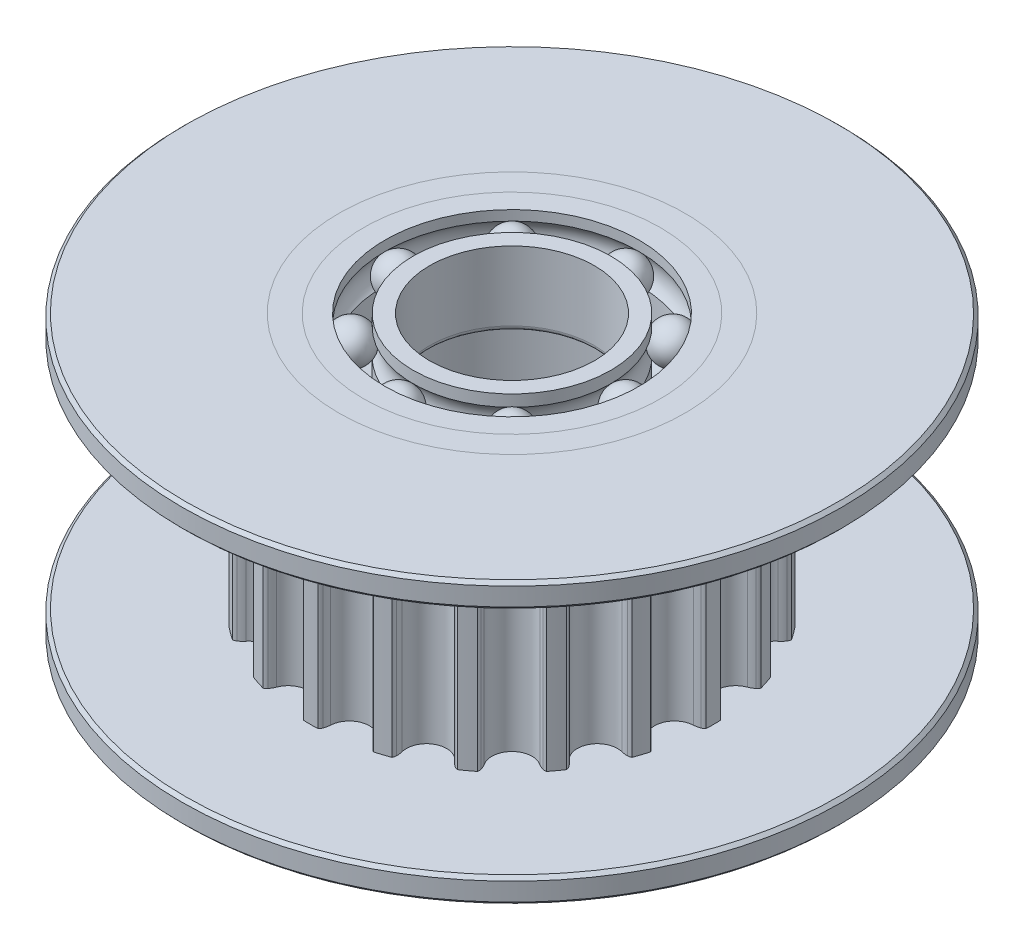
SolidWorks part; units mm, degrees
material "6061-T6 (SS)"
ref_plane "Přední rovina" through (0, 0, 0) normal (0, 0, 1) x (1, 0, 0)
ref_plane "Horní rovina" through (0, 0, 0) normal (0, 1, 0) x (1, 0, 0)
ref_plane "Pravá rovina" through (0, 0, 0) normal (1, 0, 0) x (0, 0, -1)
sketch "Skica1" plane through (0, 0, 0) normal (0, 0, 1) x (1, 0, 0)
  line L0 (4.5, 10) -> (5.25, 10)
  line L1 (5.25, 10) -> (5.25, 8.5)
  line L2 (5.25, 8.5) -> (6.11, 8.5)
  line L3 (6.11, 8.5) -> (6.11, 1.5)
  line L4 (6.11, 1.5) -> (5.25, 1.5)
  line L5 (5.25, 1.5) -> (5.25, 0)
  line L6 (5.25, 0) -> (4.5, 0)
  line L8 (4.5, 10) -> (4.5, 7)
  line L9 (4.5, 7) -> (3.5, 7)
  line L10 (3.5, 7) -> (3.5, 3)
  line L11 (3.5, 3) -> (4.5, 3)
  line L12 (4.5, 3) -> (4.5, 0)
  line L13 (0, 0) -> (0, -4.1646) construction
  dimension "D1" = 10
  dimension "D2" = 7
  dimension "D3" = 4.5
  dimension "D4" = 3.5
  dimension "D5" = 6.11
  dimension "D6" = 3
  dimension "D7" = 5.25
revolve "Rotovat1" add sketch "Skica1" angle 360 about L13
chamfer "Zkosení1" distance 0.1 angle 45 4 edges at (0, 3, 3.5) (0, 0, 4.5) (0, 7, 3.5) (0, 10, 4.5)
fillet "Zaoblit1" radius 0.1 2 edges at (0, 3, 4.5) (0, 7, 4.5)
sketch "Skica11" plane through (0, 8.5, 0) normal (0, 1, 0) x (1, 0, 0)
  line L0 (0, -5.5) -> (0, 5.5) construction
  line L1 (-5.5, 0) -> (5.5, 0) construction
  point P5 (0, 6.1087)
  arc B0 (-3.6824, -4.5256) -> (-4.5256, -3.6824) centre (-4.1938, -4.1938) ccw
  arc B1 (-3.6824, -4.5256) -> (-3.7624, -4.7003) centre (-3.1284, -4.885) ccw
  arc B2 (-3.7624, -4.7003) -> (-3.7672, -4.8088) centre (-3.5429, -4.7643) ccw
  arc B3 (-3.7672, -4.8088) -> (-3.4093, -5.0688) centre (0, 0) ccw
  arc B4 (-3.4093, -5.0688) -> (-3.3076, -5.0308) centre (-3.4362, -4.8418) ccw
  arc B5 (-3.3076, -5.0308) -> (-3.1662, -4.9006) centre (-3.6792, -4.4848) ccw
  arc B6 (-2.1037, -5.442) -> (-3.1662, -4.9006) centre (-2.6926, -5.2845) ccw
  arc B7 (-2.1037, -5.442) -> (-2.1258, -5.6329) centre (-1.4657, -5.6126) ccw
  arc B8 (-2.1258, -5.6329) -> (-2.0968, -5.7376) centre (-1.8973, -5.6259) ccw
  arc B9 (-2.0968, -5.7376) -> (-1.6761, -5.8742) centre (0, 0) ccw
  arc B10 (-1.6761, -5.8742) -> (-1.5911, -5.8066) centre (-1.7719, -5.6667) ccw
  arc B11 (-1.5911, -5.8066) -> (-1.4968, -5.6392) centre (-2.1132, -5.4022) ccw
  arc B12 (-0.319, -5.8257) -> (-1.4968, -5.6392) centre (-0.9278, -5.8579) ccw
  arc B13 (-0.319, -5.8257) -> (-0.2811, -6.0141) centre (0.3404, -5.7909) ccw
  arc B14 (-0.2811, -6.0141) -> (-0.2211, -6.1047) centre (-0.0659, -5.9369) ccw
  arc B15 (-0.2211, -6.1047) -> (0.2211, -6.1047) centre (0, 0) ccw
  arc B16 (0.2211, -6.1047) -> (0.2811, -6.0141) centre (0.0659, -5.9369) ccw
  arc B17 (0.2811, -6.0141) -> (0.319, -5.8257) centre (-0.3404, -5.7909) ccw
  arc B18 (1.4968, -5.6392) -> (0.319, -5.8257) centre (0.9278, -5.8579) ccw
  arc B19 (1.4968, -5.6392) -> (1.5911, -5.8066) centre (2.1132, -5.4022) ccw
  arc B20 (1.5911, -5.8066) -> (1.6761, -5.8742) centre (1.7719, -5.6667) ccw
  arc B21 (1.6761, -5.8742) -> (2.0968, -5.7376) centre (0, 0) ccw
  arc B22 (2.0968, -5.7376) -> (2.1258, -5.6329) centre (1.8973, -5.6259) ccw
  arc B23 (2.1258, -5.6329) -> (2.1037, -5.442) centre (1.4657, -5.6126) ccw
  arc B24 (3.1662, -4.9006) -> (2.1037, -5.442) centre (2.6926, -5.2845) ccw
  arc B25 (3.1662, -4.9006) -> (3.3076, -5.0308) centre (3.6792, -4.4848) ccw
  arc B26 (3.3076, -5.0308) -> (3.4093, -5.0688) centre (3.4362, -4.8418) ccw
  arc B27 (3.4093, -5.0688) -> (3.7672, -4.8088) centre (0, 0) ccw
  arc B28 (3.7672, -4.8088) -> (3.7624, -4.7003) centre (3.5429, -4.7643) ccw
  arc B29 (3.7624, -4.7003) -> (3.6824, -4.5256) centre (3.1284, -4.885) ccw
  arc B30 (4.5256, -3.6824) -> (3.6824, -4.5256) centre (4.1938, -4.1938) ccw
  arc B31 (4.5256, -3.6824) -> (4.7003, -3.7624) centre (4.885, -3.1284) ccw
  arc B32 (4.7003, -3.7624) -> (4.8088, -3.7672) centre (4.7643, -3.5429) ccw
  arc B33 (4.8088, -3.7672) -> (5.0688, -3.4093) centre (0, 0) ccw
  arc B34 (5.0688, -3.4093) -> (5.0308, -3.3076) centre (4.8418, -3.4362) ccw
  arc B35 (5.0308, -3.3076) -> (4.9006, -3.1662) centre (4.4848, -3.6792) ccw
  arc B36 (5.442, -2.1037) -> (4.9006, -3.1662) centre (5.2845, -2.6926) ccw
  arc B37 (5.442, -2.1037) -> (5.6329, -2.1258) centre (5.6126, -1.4657) ccw
  arc B38 (5.6329, -2.1258) -> (5.7376, -2.0968) centre (5.6259, -1.8973) ccw
  arc B39 (5.7376, -2.0968) -> (5.8742, -1.6761) centre (0, 0) ccw
  arc B40 (5.8742, -1.6761) -> (5.8066, -1.5911) centre (5.6667, -1.7719) ccw
  arc B41 (5.8066, -1.5911) -> (5.6392, -1.4968) centre (5.4022, -2.1132) ccw
  arc B42 (5.8257, -0.319) -> (5.6392, -1.4968) centre (5.8579, -0.9278) ccw
  arc B43 (5.8257, -0.319) -> (6.0141, -0.2811) centre (5.7909, 0.3404) ccw
  arc B44 (6.0141, -0.2811) -> (6.1047, -0.2211) centre (5.9369, -0.0659) ccw
  arc B45 (6.1047, -0.2211) -> (6.1047, 0.2211) centre (0, 0) ccw
  arc B46 (6.1047, 0.2211) -> (6.0141, 0.2811) centre (5.9369, 0.0659) ccw
  arc B47 (6.0141, 0.2811) -> (5.8257, 0.319) centre (5.7909, -0.3404) ccw
  arc B48 (5.6392, 1.4968) -> (5.8257, 0.319) centre (5.8579, 0.9278) ccw
  arc B49 (5.6392, 1.4968) -> (5.8066, 1.5911) centre (5.4022, 2.1132) ccw
  arc B50 (5.8066, 1.5911) -> (5.8742, 1.6761) centre (5.6667, 1.7719) ccw
  arc B51 (5.8742, 1.6761) -> (5.7376, 2.0968) centre (0, 0) ccw
  arc B52 (5.7376, 2.0968) -> (5.6329, 2.1258) centre (5.6259, 1.8973) ccw
  arc B53 (5.6329, 2.1258) -> (5.442, 2.1037) centre (5.6126, 1.4657) ccw
  arc B54 (4.9006, 3.1662) -> (5.442, 2.1037) centre (5.2845, 2.6926) ccw
  arc B55 (4.9006, 3.1662) -> (5.0308, 3.3076) centre (4.4848, 3.6792) ccw
  arc B56 (5.0308, 3.3076) -> (5.0688, 3.4093) centre (4.8418, 3.4362) ccw
  arc B57 (5.0688, 3.4093) -> (4.8088, 3.7672) centre (0, 0) ccw
  arc B58 (4.8088, 3.7672) -> (4.7003, 3.7624) centre (4.7643, 3.5429) ccw
  arc B59 (4.7003, 3.7624) -> (4.5256, 3.6824) centre (4.885, 3.1284) ccw
  arc B60 (3.6824, 4.5256) -> (4.5256, 3.6824) centre (4.1938, 4.1938) ccw
  arc B61 (3.6824, 4.5256) -> (3.7624, 4.7003) centre (3.1284, 4.885) ccw
  arc B62 (3.7624, 4.7003) -> (3.7672, 4.8088) centre (3.5429, 4.7643) ccw
  arc B63 (3.7672, 4.8088) -> (3.4093, 5.0688) centre (0, 0) ccw
  arc B64 (3.4093, 5.0688) -> (3.3076, 5.0308) centre (3.4362, 4.8418) ccw
  arc B65 (3.3076, 5.0308) -> (3.1662, 4.9006) centre (3.6792, 4.4848) ccw
  arc B66 (2.1037, 5.442) -> (3.1662, 4.9006) centre (2.6926, 5.2845) ccw
  arc B67 (2.1037, 5.442) -> (2.1258, 5.6329) centre (1.4657, 5.6126) ccw
  arc B68 (2.1258, 5.6329) -> (2.0968, 5.7376) centre (1.8973, 5.6259) ccw
  arc B69 (2.0968, 5.7376) -> (1.6761, 5.8742) centre (0, 0) ccw
  arc B70 (1.6761, 5.8742) -> (1.5911, 5.8066) centre (1.7719, 5.6667) ccw
  arc B71 (1.5911, 5.8066) -> (1.4968, 5.6392) centre (2.1132, 5.4022) ccw
  arc B72 (0.319, 5.8257) -> (1.4968, 5.6392) centre (0.9278, 5.8579) ccw
  arc B73 (0.319, 5.8257) -> (0.2811, 6.0141) centre (-0.3404, 5.7909) ccw
  arc B74 (0.2811, 6.0141) -> (0.2211, 6.1047) centre (0.0659, 5.9369) ccw
  arc B75 (0.2211, 6.1047) -> (-0.2211, 6.1047) centre (0, 0) ccw
  arc B76 (-0.2211, 6.1047) -> (-0.2811, 6.0141) centre (-0.0659, 5.9369) ccw
  arc B77 (-0.2811, 6.0141) -> (-0.319, 5.8257) centre (0.3404, 5.7909) ccw
  arc B78 (-1.4968, 5.6392) -> (-0.319, 5.8257) centre (-0.9278, 5.8579) ccw
  arc B79 (-1.4968, 5.6392) -> (-1.5911, 5.8066) centre (-2.1132, 5.4022) ccw
  arc B80 (-1.5911, 5.8066) -> (-1.6761, 5.8742) centre (-1.7719, 5.6667) ccw
  arc B81 (-1.6761, 5.8742) -> (-2.0968, 5.7376) centre (0, 0) ccw
  arc B82 (-2.0968, 5.7376) -> (-2.1258, 5.6329) centre (-1.8973, 5.6259) ccw
  arc B83 (-2.1258, 5.6329) -> (-2.1037, 5.442) centre (-1.4657, 5.6126) ccw
  arc B84 (-3.1662, 4.9006) -> (-2.1037, 5.442) centre (-2.6926, 5.2845) ccw
  arc B85 (-3.1662, 4.9006) -> (-3.3076, 5.0308) centre (-3.6792, 4.4848) ccw
  arc B86 (-3.3076, 5.0308) -> (-3.4093, 5.0688) centre (-3.4362, 4.8418) ccw
  arc B87 (-3.4093, 5.0688) -> (-3.7672, 4.8088) centre (0, 0) ccw
  arc B88 (-3.7672, 4.8088) -> (-3.7624, 4.7003) centre (-3.5429, 4.7643) ccw
  arc B89 (-3.7624, 4.7003) -> (-3.6824, 4.5256) centre (-3.1284, 4.885) ccw
  arc B90 (-4.5256, 3.6824) -> (-3.6824, 4.5256) centre (-4.1938, 4.1938) ccw
  arc B91 (-4.5256, 3.6824) -> (-4.7003, 3.7624) centre (-4.885, 3.1284) ccw
  arc B92 (-4.7003, 3.7624) -> (-4.8088, 3.7672) centre (-4.7643, 3.5429) ccw
  arc B93 (-4.8088, 3.7672) -> (-5.0688, 3.4093) centre (0, 0) ccw
  arc B94 (-5.0688, 3.4093) -> (-5.0308, 3.3076) centre (-4.8418, 3.4362) ccw
  arc B95 (-5.0308, 3.3076) -> (-4.9006, 3.1662) centre (-4.4848, 3.6792) ccw
  arc B96 (-5.442, 2.1037) -> (-4.9006, 3.1662) centre (-5.2845, 2.6926) ccw
  arc B97 (-5.442, 2.1037) -> (-5.6329, 2.1258) centre (-5.6126, 1.4657) ccw
  arc B98 (-5.6329, 2.1258) -> (-5.7376, 2.0968) centre (-5.6259, 1.8973) ccw
  arc B99 (-5.7376, 2.0968) -> (-5.8742, 1.6761) centre (0, 0) ccw
  arc B100 (-5.8742, 1.6761) -> (-5.8066, 1.5911) centre (-5.6667, 1.7719) ccw
  arc B101 (-5.8066, 1.5911) -> (-5.6392, 1.4968) centre (-5.4022, 2.1132) ccw
  arc B102 (-5.8257, 0.319) -> (-5.6392, 1.4968) centre (-5.8579, 0.9278) ccw
  arc B103 (-5.8257, 0.319) -> (-6.0141, 0.2811) centre (-5.7909, -0.3404) ccw
  arc B104 (-6.0141, 0.2811) -> (-6.1047, 0.2211) centre (-5.9369, 0.0659) ccw
  arc B105 (-6.1047, 0.2211) -> (-6.1047, -0.2211) centre (0, 0) ccw
  arc B106 (-6.1047, -0.2211) -> (-6.0141, -0.2811) centre (-5.9369, -0.0659) ccw
  arc B107 (-6.0141, -0.2811) -> (-5.8257, -0.319) centre (-5.7909, 0.3404) ccw
  arc B108 (-5.6392, -1.4968) -> (-5.8257, -0.319) centre (-5.8579, -0.9278) ccw
  arc B109 (-5.6392, -1.4968) -> (-5.8066, -1.5911) centre (-5.4022, -2.1132) ccw
  arc B110 (-5.8066, -1.5911) -> (-5.8742, -1.6761) centre (-5.6667, -1.7719) ccw
  arc B111 (-5.8742, -1.6761) -> (-5.7376, -2.0968) centre (0, 0) ccw
  arc B112 (-5.7376, -2.0968) -> (-5.6329, -2.1258) centre (-5.6259, -1.8973) ccw
  arc B113 (-5.6329, -2.1258) -> (-5.442, -2.1037) centre (-5.6126, -1.4657) ccw
  arc B114 (-4.9006, -3.1662) -> (-5.442, -2.1037) centre (-5.2845, -2.6926) ccw
  arc B115 (-4.9006, -3.1662) -> (-5.0308, -3.3076) centre (-4.4848, -3.6792) ccw
  arc B116 (-5.0308, -3.3076) -> (-5.0688, -3.4093) centre (-4.8418, -3.4362) ccw
  arc B117 (-5.0688, -3.4093) -> (-4.8088, -3.7672) centre (0, 0) ccw
  arc B118 (-4.8088, -3.7672) -> (-4.7003, -3.7624) centre (-4.7643, -3.5429) ccw
  arc B119 (-4.7003, -3.7624) -> (-4.5256, -3.6824) centre (-4.885, -3.1284) ccw
sketch_block_instance "Blok1-1"
sketch_block "Blok1"
extrude "Odebrat vysunutím1" cut sketch "Skica11" against normal through all flip side to cut
sketch "Skica10" plane through (0, 10, 0) normal (0, 1, 0) x (1, 0, 0)
  circle A0 centre (0, 0) radius 10
  circle A1 centre (0, 0) radius 5.25 construction
  circle A2 centre (0, 0) radius 5.25
  dimension "D1" = 20
extrude "Přidat vysunutím1" add sketch "Skica10" against normal up to surface (1.5 mm away) separate body up to face at (0, 8.5, 5.25)
sketch "Skica12" plane through (0, 0, 0) normal (0, -1, 0) x (1, 0, 0)
  circle A0 centre (0, 0) radius 10
  circle A1 centre (0, 0) radius 5.25 construction
  circle A2 centre (0, 0) radius 5.25
  circle A3 centre (0, 0) radius 10 construction
extrude "Přidat vysunutím2" add sketch "Skica12" against normal up to surface (1.5 mm away) separate body up to face at (0, 1.5, 5.25)
chamfer "Zkosení2" distance 0.1 angle 45 2 edges at (0, 8.5, -10) (0, 10, 10)
chamfer "Zkosení3" distance 0.1 angle 45 2 edges at (0, 0, -10) (0, 1.5, 10)
sketch "Skica4" plane through (0, 0, 0) normal (0, 0, 1) x (1, 0, 0)
  line L0 (4.5, 9.85) -> (4.5, 7.15)
  line L1 (4.35, 7) -> (4.2, 7)
  line L2 (4.2, 7) -> (4.2, 7.05)
  line L3 (3.85, 7.2828) -> (4.2132, 7.229)
  line L4 (3.85, 7.2828) -> (3.85, 8.0528)
  line L5 (3.85, 8.9472) -> (3.85, 9.7172)
  line L6 (3.85, 9.7172) -> (4.2132, 9.771)
  line L7 (4.35, 10) -> (4.2, 10)
  line L8 (4.2, 10) -> (4.2, 9.95)
  line L9 (0, 0) -> (0, 18.4294) construction
  line L10 (4.4, 7) -> (-4.4, 7) construction
  arc A0 (4.35, 10) -> (4.5, 9.85) centre (4.35, 9.85) cw
  arc A1 (4.35, 7) -> (4.5, 7.15) centre (4.35, 7.15) ccw
  arc A2 (4.2, 9.95) -> (4.2132, 9.771) centre (4.2, 9.86) cw
  arc A3 (3.85, 8.9472) -> (3.85, 8.0528) centre (3.45, 8.5) cw
  arc A4 (4.2, 7.05) -> (4.2132, 7.229) centre (4.2, 7.14) ccw
  point P26 (4.5, 8.5)
  point P29 (4.275, 7)
  dimension "D3" = 0.09
  dimension "D6" = 0.15
  dimension "D7" = 0.6
  dimension "D1" = 4.5
  dimension "D2" = 3.85
  dimension "D4" = 0.05
  dimension "D5" = 0.15
  dimension "D8" = 0.77
  dimension "D9" = 3
  dimension "D10" = 1.05
revolve "Rotovat2" add sketch "Skica4" angle 360 about L9
sketch "Skica5" plane through (0, 0, 0) normal (0, 0, 1) x (1, 0, 0)
  line L0 (2.5, 9.85) -> (2.5, 7.15)
  line L1 (2.65, 10) -> (2.97, 10)
  line L2 (3, 9.97) -> (3, 9.86)
  line L3 (3, 9.86) -> (3.6, 9.86)
  line L4 (3.6, 9.86) -> (3.9, 9.84)
  line L5 (3.9, 9.84) -> (4.2, 9.86)
  line L6 (4.2, 9.86) -> (4.2, 9.81)
  line L7 (4.2, 9.81) -> (3.9, 9.77)
  line L8 (3.9, 9.77) -> (3.6, 9.77)
  line L9 (3.6, 9.77) -> (3, 9.81)
  line L10 (3, 9.81) -> (3, 8.8969)
  line L11 (2.65, 7) -> (2.97, 7)
  line L12 (0, 0) -> (0, 20.363) construction
  line L13 (3, 7.03) -> (3, 7.14)
  line L21 (3, 7.19) -> (3, 8.1031)
  line L22 (3, 7.14) -> (3.6, 7.14)
  line L23 (3.6, 7.14) -> (3.8962, 7.1917)
  line L24 (3.8962, 7.1917) -> (4.1924, 7.14)
  line L25 (4.1924, 7.14) -> (4.1924, 7.19)
  line L26 (4.1924, 7.19) -> (3.8975, 7.2581)
  line L27 (3.8975, 7.2581) -> (3.5975, 7.2581)
  line L28 (3.5975, 7.2581) -> (3, 7.19)
  line L29 (-4.2, 7) -> (4.2, 7) construction
  arc A0 (2.65, 7) -> (2.5, 7.15) centre (2.65, 7.15) cw
  arc A1 (2.65, 10) -> (2.5, 9.85) centre (2.65, 9.85) ccw
  arc A2 (3, 9.97) -> (2.97, 10) centre (2.97, 9.97) ccw
  arc A3 (3, 7.03) -> (2.97, 7) centre (2.97, 7.03) cw
  arc A4 (3, 8.8969) -> (3, 8.1031) centre (3.45, 8.5) ccw
  dimension "D3" = 0.15
  dimension "D4" = 0.11
  dimension "D5" = 0.03
  dimension "D7" = 0.6
  dimension "D1" = 2.5
  dimension "D2" = 3
  dimension "D6" = 0.6
  dimension "D8" = 0.95
  dimension "D9" = 3
  dimension "D10" = 1.2
  dimension "D11" = 0.3
  dimension "D12" = 0.05
  dimension "D13" = 0.9
  dimension "D14" = 0.6
  dimension "D15" = 0.09
  dimension "D16" = 0.05
  dimension "D17" = 0.05
revolve "Rotovat3" add sketch "Skica5" angle 360 about L12
sketch "Skica6" plane through (0, 0, 0) normal (0, 0, 1) x (1, 0, 0)
  line L0 (3.45, 9.1) -> (3.45, 7.9)
  line L4 (-4.2, 7) -> (4.2, 7) construction
  arc A0 (3.45, 9.1) -> (3.45, 7.9) centre (3.45, 8.5) cw
  dimension "D1" = 0.6
  dimension "D2" = 1.5
  dimension "D3" = 3.45
revolve "Rotovat4" add sketch "Skica6" angle 360 about L0
pattern_circular "Kruhové pole1" count 8 over 360 about axis through (0, 0, 0) along (0, 1, 0) of bodies 105
sketch "Skica7" plane through (0, 0, 0) normal (0, 0, 1) x (1, 0, 0)
  line L0 (4.5, 2.85) -> (4.5, 0.15)
  line L1 (4.35, 0) -> (4.2, 0)
  line L2 (4.2, 0) -> (4.2, 0.05)
  line L3 (3.85, 0.2828) -> (4.2132, 0.229)
  line L4 (3.85, 0.2828) -> (3.85, 1.0528)
  line L5 (3.85, 1.9472) -> (3.85, 2.7172)
  line L6 (3.85, 2.7172) -> (4.2132, 2.771)
  line L7 (4.35, 3) -> (4.2, 3)
  line L8 (4.2, 3) -> (4.2, 2.95)
  line L9 (0, 0) -> (0, 11.2374) construction
  arc A0 (4.35, 3) -> (4.5, 2.85) centre (4.35, 2.85) cw
  arc A1 (4.35, 0) -> (4.5, 0.15) centre (4.35, 0.15) ccw
  arc A2 (4.2, 2.95) -> (4.2132, 2.771) centre (4.2, 2.86) cw
  arc A3 (3.85, 1.9472) -> (3.85, 1.0528) centre (3.45, 1.5) cw
  arc A4 (4.2, 0.05) -> (4.2132, 0.229) centre (4.2, 0.14) ccw
  point P19 (4.5, 1.5)
  point P20 (4.275, 0)
  dimension "D1" = 0.09
  dimension "D4" = 0.15
  dimension "D5" = 0.6
  dimension "D2" = 0.05
  dimension "D3" = 0.15
  dimension "D6" = 0.77
  dimension "D7" = 3
  dimension "D8" = 1.05
  dimension "D9" = 4.5
  dimension "D10" = 3.85
revolve "Rotovat5" add sketch "Skica7" angle 360 about L9
sketch "Skica8" plane through (0, 0, 0) normal (0, 0, 1) x (1, 0, 0)
  line L0 (2.5, 2.85) -> (2.5, 0.15)
  line L1 (2.65, 3) -> (2.97, 3)
  line L2 (3, 2.97) -> (3, 2.86)
  line L3 (3, 2.86) -> (3.6, 2.86)
  line L4 (3.6, 2.86) -> (3.9, 2.84)
  line L5 (3.9, 2.84) -> (4.2, 2.86)
  line L6 (4.2, 2.86) -> (4.2, 2.81)
  line L7 (4.2, 2.81) -> (3.9, 2.77)
  line L8 (3.9, 2.77) -> (3.6, 2.77)
  line L9 (3.6, 2.77) -> (3, 2.81)
  line L10 (3, 2.81) -> (3, 1.8969)
  line L11 (2.65, 0) -> (2.97, 0)
  line L12 (3, 0.03) -> (3, 0.14)
  line L13 (3, 0.19) -> (3, 1.1031)
  line L14 (3, 0.14) -> (3.6, 0.14)
  line L15 (3.6, 0.14) -> (3.8962, 0.1917)
  line L16 (3.8962, 0.1917) -> (4.1924, 0.14)
  line L17 (4.1924, 0.14) -> (4.1924, 0.19)
  line L18 (4.1924, 0.19) -> (3.8975, 0.2581)
  line L19 (3.8975, 0.2581) -> (3.5975, 0.2581)
  line L20 (3.5975, 0.2581) -> (3, 0.19)
  line L21 (0, 0) -> (0, -2.9362) construction
  arc A0 (2.65, 0) -> (2.5, 0.15) centre (2.65, 0.15) cw
  arc A1 (2.65, 3) -> (2.5, 2.85) centre (2.65, 2.85) ccw
  arc A2 (3, 2.97) -> (2.97, 3) centre (2.97, 2.97) ccw
  arc A3 (3, 0.03) -> (2.97, 0) centre (2.97, 0.03) cw
  arc A4 (3, 1.8969) -> (3, 1.1031) centre (3.45, 1.5) ccw
  dimension "D1" = 0.15
  dimension "D2" = 0.03
  dimension "D5" = 0.6
  dimension "D3" = 0.11
  dimension "D4" = 0.6
  dimension "D6" = 0.95
  dimension "D7" = 3
  dimension "D8" = 1.2
  dimension "D9" = 0.3
  dimension "D10" = 0.05
  dimension "D11" = 0.9
  dimension "D12" = 0.6
  dimension "D13" = 0.09
  dimension "D14" = 0.05
  dimension "D15" = 0.05
  dimension "D16" = 2.5
  dimension "D17" = 3
revolve "Rotovat6" add sketch "Skica8" angle 360 about L21
sketch "Skica9" plane through (0, 0, 0) normal (0, 0, 1) x (1, 0, 0)
  line L0 (3.45, 2.1) -> (3.45, 0.9)
  line L1 (0, -2.351) -> (0, 5.6956) construction
  arc A0 (3.45, 2.1) -> (3.45, 0.9) centre (3.45, 1.5) cw
  dimension "D1" = 0.6
  dimension "D2" = 3.45
  dimension "D3" = 1.5
revolve "Rotovat7" add sketch "Skica9" angle 360 about L0
pattern_circular "Kruhové pole3" count 8 over 360 about axis through (0, 0, 0) along (0, 1, 0) reverse direction yes of bodies 123
sketch "Sketch1" plane through (0, 0, 0) normal (0, -1, 0) x (1, 0, 0)
  circle A0 centre (0, 0) radius 15.3295
extrude "Cut-Extrude1" cut sketch "Sketch1" against normal blind 0.75
extrude "Cut-Extrude2" cut sketch "Sketch1<2>" along normal blind 0.75 from surface starting at face at (0, 10, 9.9)
sketch "Sketch1<2>" plane through (0, 0, 0) normal (0, -1, 0) x (1, 0, 0) same geometry as "Sketch1"
chamfer "Chamfer1" distance 0.1 angle 45 1 edges at (0, 9.25, 10)
chamfer "Chamfer2" distance 0.1 angle 45 1 edges at (0, 0.75, -10)
